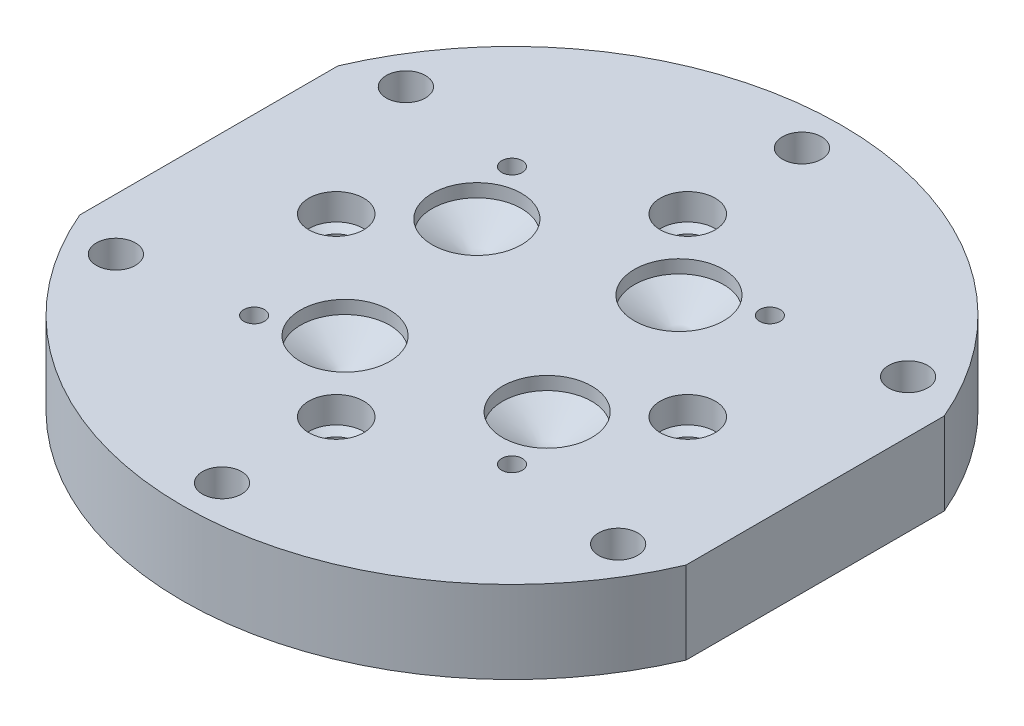
SolidWorks part; units mm, degrees
material "Copper"
ref_plane "Front Plane" through (0, 0, 0) normal (0, 0, 1) x (1, 0, 0)
ref_plane "Top Plane" through (0, 0, 0) normal (0, 1, 0) x (1, 0, 0)
ref_plane "Right Plane" through (0, 0, 0) normal (1, 0, 0) x (0, 0, -1)
ref_axis "Y Axis" through (0, 0.1588, 0) along (0, -1, 0)
sketch "outer" plane through (0, 0, 0) normal (0, 1, 0) x (1, 0, 0)
  circle A0 centre (0, 0) radius 19.05
  dimension "D1" = 38.1
extrude "Body" add sketch "outer" against normal blind 4.7625
sketch "Screw Position" plane through (0, 0, 0) normal (0, 1, 0) x (1, 0, 0)
  point P0 (0, -16.764)
  dimension "D1" = 16.764
hole_wizard "#4-40 Tapped Hole" positions "Sketch12" profile "Sketch13" tap size "#4-40" standard "ANSI Inch" end condition through all
sketch "Sketch12" plane through (0, 0, 0) normal (0, 1, 0) x (1, 0, 0)
  point P0 (0, -16.764)
sketch "Sketch13" plane through (0, 0, 16.764) normal (1, 0, 0) x (0, 0, 1)
  line L0 (0, 0) -> (0, 4.7625)
  line L1 (0, 4.7625) -> (1.1303, 4.7625)
  line L2 (1.1303, 4.7625) -> (1.1303, 0)
  line L5 (1.1303, 0) -> (0, 0)
  line L11 (0, -6.35) -> (0, 107.95) construction
  dimension "Thru Tap Drill Dia." = 2.2606
  dimension "Thru Tap Drill Depth" = 4.7625
cosmetic thread "Hole Thread3" parameters "D2"=2.8448
pattern_circular "Screw Holes" count 6 over 360 about axis through (0, 0.1588, 0) along (0, -1, 0) of "#4-40 Tapped Hole"
sketch "inner" plane through (0, 0, 0) normal (0, 1, 0) x (1, 0, 0)
  circle A0 centre (0, 0) radius 11.938
  dimension "D1" = 23.876
sketch "Inner Screw Position" plane through (0, 0, 0) normal (0, 1, 0) x (1, 0, 0)
  point P0 (-7.4536, 7.4536)
  dimension "D1" = 10.541
hole_wizard "#0-80 Tapped Hole" positions "Sketch34" profile "Sketch35" tap size "#0-80" standard "ANSI Inch" end condition through all
sketch "Sketch34" plane through (0, 0, 0) normal (0, 1, 0) x (1, 0, 0)
  point P0 (-7.4536, 7.4536)
sketch "Sketch35" plane through (-7.4536, 0, -7.4536) normal (1, 0, 0) x (0, 0, 1)
  line L0 (0, 0) -> (0, 4.7625)
  line L1 (0, 4.7625) -> (0.5956, 4.7625)
  line L2 (0.5956, 4.7625) -> (0.5956, 0)
  line L5 (0.5956, 0) -> (0, 0)
  line L11 (0, -6.35) -> (0, 107.95) construction
  dimension "Thru Tap Drill Dia." = 1.1913
  dimension "Thru Tap Drill Depth" = 4.7625
cosmetic thread "Hole Thread4" parameters "D2"=1.524
pattern_circular "Inner Screw Holes" count 4 over 360 about axis through (0, 0.1588, 0) along (0, -1, 0) of "#0-80 Tapped Hole"
sketch "IO Hole Location" plane through (0, 0, 0) normal (0, 1, 0) x (1, 0, 0)
  point P0 (0, 10.16)
hole_wizard "#43 (0.089) Diameter Hole1" positions "Sketch36" profile "Sketch37" hole size "#43" standard "ANSI Inch" end condition through all
sketch "Sketch36" plane through (0, 0, 0) normal (0, 1, 0) x (1, 0, 0)
  point P0 (0, 10.16)
sketch "Sketch37" plane through (0, 0, -10.16) normal (1, 0, 0) x (0, 0, 1)
  line L0 (0, 0) -> (0, 4.7625)
  line L1 (0, 4.7625) -> (1.1303, 4.7625)
  line L2 (1.1303, 4.7625) -> (1.1303, 0)
  line L5 (1.1303, 0) -> (0, 0)
  line L11 (0, -6.35) -> (0, 107.95) construction
  dimension "Thru Hole Dia." = 2.2606
  dimension "Thru Hole Depth" = 4.7625
hole_wizard "1/8 (0.125) Diameter Hole1" positions "Sketch38" profile "Sketch40" hole size "1/8" standard "ANSI Inch"
sketch "Sketch38" plane through (0, 0, 0) normal (0, 1, 0) x (1, 0, 0)
  point P0 (0, 10.16)
sketch "Sketch40" plane through (0, 0, -10.16) normal (1, 0, 0) x (0, 0, 1)
  line L0 (0, 0) -> (0, 2.4779)
  line L1 (0, 2.4779) -> (1.5875, 1.524)
  line L2 (1.5875, 1.524) -> (1.5875, 0)
  line L5 (1.5875, 0) -> (0, 0)
  line L10 (0, 2.4779) -> (-1.5875, 1.524) construction
  line L11 (0, -6.35) -> (0, 107.95) construction
  dimension "Hole Dia." = 3.175
  dimension "Hole Depth" = 1.524
  dimension "Drill Angle" = 118
hole_wizard "1/8 (0.125) Diameter Hole2" positions "Sketch41" profile "Sketch42" hole size "1/8" standard "ANSI Inch"
sketch "Sketch41" plane through (0, -4.7625, 0) normal (0, -1, 0) x (-1, 0, 0)
  point P0 (0, 10.16)
sketch "Sketch42" plane through (0, -4.7625, -10.16) normal (1, 0, 0) x (0, 0, -1)
  line L0 (0, 0) -> (0, 2.4779)
  line L1 (0, 2.4779) -> (1.5875, 1.524)
  line L2 (1.5875, 1.524) -> (1.5875, 0)
  line L5 (1.5875, 0) -> (0, 0)
  line L10 (0, 2.4779) -> (-1.5875, 1.524) construction
  line L11 (0, -6.35) -> (0, 107.95) construction
  dimension "Hole Dia." = 3.175
  dimension "Hole Depth" = 1.524
  dimension "Drill Angle" = 118
pattern_circular "IO Holes Pattern" count 4 over 360 about axis through (0, 0.1588, 0) along (0, -1, 0) of "#43 (0.089) Diameter Hole1", "1/8 (0.125) Diameter Hole1", "1/8 (0.125) Diameter Hole2"
sketch "Post Bottom Location" plane through (0, 0, 0) normal (0, 1, 0) x (1, 0, 0)
  point P0 (3.81, 5.842)
  point P1 (0, 0)
  point P4 (0, 0)
  point P5 (2.1187, 3.6372)
  point P6 (8.1218, 5.544)
  point P7 (0, 0)
  point P8 (0, 0)
  dimension "D1" = 3.81
  dimension "D2" = 5.842
hole_wizard "13/64 (0.20313) Diameter Hole1" positions "Sketch44" profile "Sketch45" hole size "13/64" standard "ANSI Inch"
sketch "Sketch44" plane through (0, 0, 0) normal (0, 1, 0) x (1, 0, 0)
  point P7 (3.81, 5.842)
sketch "Sketch45" plane through (3.81, 0, -5.842) normal (1, 0, 0) x (0, 0, 1)
  line L0 (0, 0) -> (0, 2.3121)
  line L1 (0, 2.3121) -> (2.5798, 0.762)
  line L2 (2.5798, 0.762) -> (2.5798, 0)
  line L5 (2.5798, 0) -> (0, 0)
  line L10 (0, 2.3121) -> (-2.5798, 0.762) construction
  line L11 (0, -6.35) -> (0, 107.95) construction
  dimension "Hole Dia." = 5.1595
  dimension "Hole Depth" = 0.762
  dimension "Drill Angle" = 118
pattern_circular "Post Bottoms" count 4 over 360 about axis through (0, 0.1588, 0) along (0, -1, 0) of "13/64 (0.20313) Diameter Hole1"
sketch "Flat Cut Sketch" plane through (0, 0, 0) normal (0, 1, 0) x (1, 0, 0)
  line L0 (-20.574, 19.05) -> (-17.526, 19.05)
  line L1 (20.574, -19.05) -> (17.526, -19.05)
  line L2 (20.574, -19.05) -> (20.574, 19.05)
  line L3 (20.574, 19.05) -> (17.526, 19.05)
  line L4 (17.526, -19.05) -> (17.526, 19.05)
  line L5 (20.574, -19.05) -> (17.526, 19.05) construction
  line L6 (20.574, 19.05) -> (17.526, -19.05) construction
  line L7 (-20.574, 19.05) -> (-20.574, -19.05)
  line L8 (-20.574, -19.05) -> (-17.526, -19.05)
  line L9 (-17.526, 19.05) -> (-17.526, -19.05)
  line L10 (-20.574, 19.05) -> (-17.526, -19.05) construction
  line L11 (-20.574, -19.05) -> (-17.526, 19.05) construction
  circle A0 centre (0, 0) radius 19.05 construction
  point P1 (19.05, 0)
  point P3 (19.05, 0)
  point P11 (-19.05, 0)
  point P12 (-19.05, 0)
  point P17 (0, 0)
  dimension "D2" = 38.1
  dimension "D3" = 2
extrude "Flat Cut" cut sketch "Flat Cut Sketch" against normal through all and the other way through all
equation "\"outer_d\"= 3 / 2in"
equation "\"screw_r\"= 0.66in"
equation "\"inner_d\"= 0.940in"
equation "\"bottom_h\"= 3 / 16in"
equation "\"pocket_h\"= 0.060in"
equation "\"screw_inner_r\"= 0.415in"
equation "\"io_r\"= 0.4in"
equation "\"D1@outer\" = \"outer_d\""
equation "\"D1@Body\" = \"bottom_h\""
equation "\"D1@inner\" = \"inner_d\""
equation "\"D1@Screw Position\" = \"screw_r\""
equation "\"D1@Inner Screw Position\" = \"screw_inner_r\""
equation "\"D1@IO Hole Location\"=\"io_r\""
equation "\"post_x\" = 0.15in"
equation "\"post_z\"= 0.23in"
equation "\"post_bottom_h\"= 0.03in"
equation "\"cut\"= 0.06in"
equation "\"D2@Flat Cut Sketch\"=\"outer_d\""
equation "\"D1@Flat Cut Sketch\"=2 * \"cut\""
equation "\"post_size\"= 0.201in"
equation "\"D1@Post Bottom Location\"=\"post_x\""
equation "\"D2@Post Bottom Location\"=\"post_z\""
